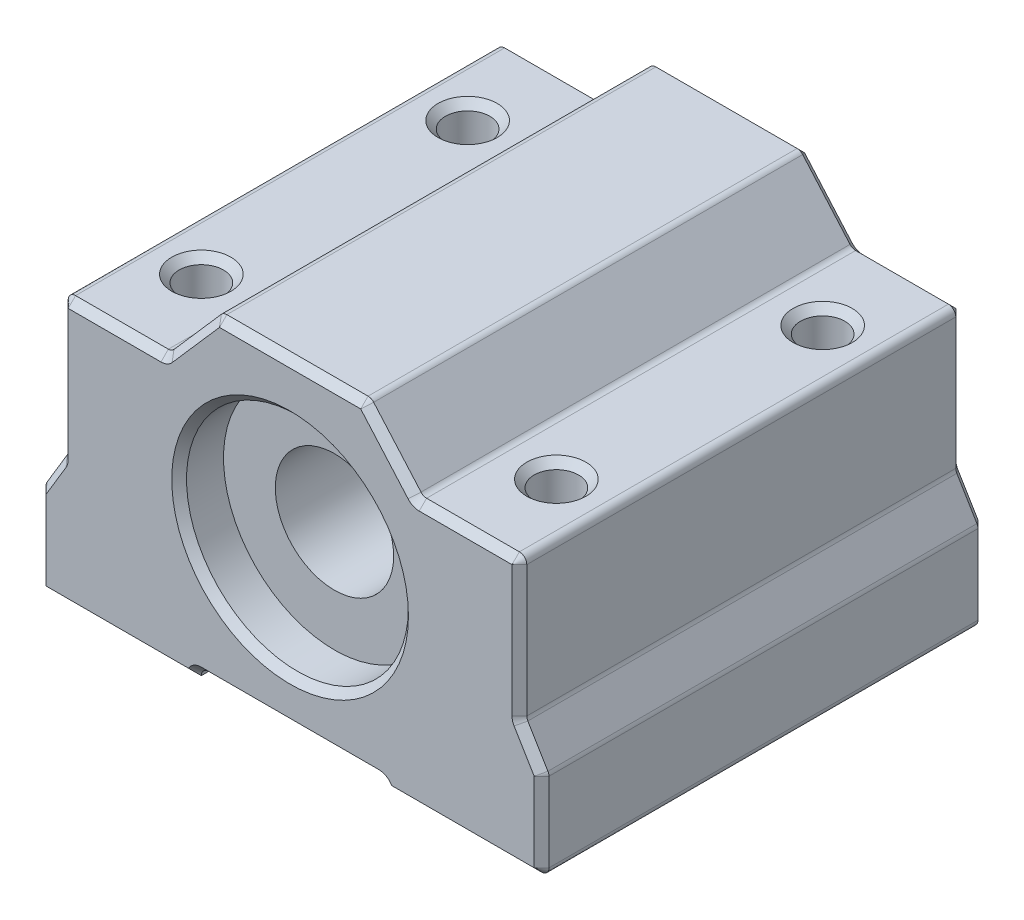
SolidWorks part; units mm, degrees
ref_plane "Front Plane" through (0, 0, 0) normal (0, 0, 1) x (1, 0, 0)
ref_plane "Top Plane" through (0, 0, 0) normal (0, 1, 0) x (1, 0, 0)
ref_plane "Right Plane" through (0, 0, 0) normal (1, 0, 0) x (0, 0, -1)
sketch "Sketch2" plane through (0, 0, 0) normal (0, 0, 1) x (1, 0, 0)
  line L17 (5, 11) -> (-5, 11)
  line L18 (-5, 11) -> (-8.5, 7)
  line L19 (-8.5, 7) -> (-15.5, 7)
  line L20 (-15.5, 7) -> (-15.5, -2.5)
  line L21 (-15.5, -2.5) -> (-17, -5)
  line L22 (-17, -5) -> (-17, -11)
  line L23 (-17, -11) -> (-6.5, -11)
  line L24 (-6.5, -11) -> (-6.5, -10.5)
  line L25 (-6.5, -10.5) -> (6.5, -10.5)
  line L26 (0, -55) -> (0, 55) construction
  line L27 (6.5, -11) -> (6.5, -10.5)
  line L28 (17, -11) -> (6.5, -11)
  line L29 (17, -5) -> (17, -11)
  line L30 (15.5, -2.5) -> (17, -5)
  line L31 (15.5, 7) -> (15.5, -2.5)
  line L32 (8.5, 7) -> (15.5, 7)
  line L33 (5, 11) -> (8.5, 7)
  circle A0 centre (0, 0) radius 7.5
  point P13 (0, -10.5)
  point P20 (0, 11)
  dimension "D12" = 15
  dimension "D1" = 31
  dimension "D2" = 0.5
  dimension "D3" = 4
  dimension "D4" = 22
  dimension "D5" = 34
  dimension "D6" = 11
  dimension "D7" = 6
  dimension "D8" = 9.5
  dimension "D9" = 13
  dimension "D10" = 10
  dimension "D11" = 7
extrude "Boss-Extrude1" add sketch "Sketch2" along normal mid plane 30
sketch "Sketch3" plane through (0, 0, 0) normal (0, 0, 1) x (1, 0, 0)
  circle A1 centre (0, 0) radius 4
  circle A2 centre (0, 0) radius 7.5
  circle A3 centre (0, 0) radius 7.5
  dimension "D2" = 8
  dimension "D1" = 0
extrude "Boss-Extrude2" add sketch "Sketch3" along normal mid plane 24 separate body
sketch "Sketch4" plane through (0, 7, 0) normal (0, 1, 0) x (1, 0, 0)
  line L0 (0, 15) -> (0, -15) construction
  line L1 (5, 15) -> (-5, 15) construction
  line L2 (5, -15) -> (-5, -15) construction
  line L3 (-15.5, 0) -> (15.5, 0) construction
  line L4 (-15.5, -15) -> (-15.5, 15) construction
  line L5 (15.5, -15) -> (15.5, 15) construction
  circle A0 centre (-12, 9) radius 1.5
  circle A1 centre (12, 9) radius 1.5
  circle A2 centre (-12, -9) radius 1.5
  circle A3 centre (12, -9) radius 1.5
  dimension "D3" = 3
  dimension "D1" = 24
  dimension "D2" = 18
extrude "Cut-Extrude1" cut sketch "Sketch4" against normal up to surface (18 mm away) up to face at (-11.75, -11, 0)
fillet "Fillet1" radius 0.5 14 edges at (6.5, -10.5, 0) (-6.5, -10.5, 0) (-17, -11, 0) (-17, -5, 0) (-15.5, -2.5, 0) (-15.5, 7, 0) (-8.5, 7, 0) (-5, 11, 0) (5, 11, 0) (8.5, 7, 0) (17, -11, 0) (17, -5, 0) (15.5, -2.5, 0) (15.5, 7, 0)
chamfer "Chamfer1" distance 0.5 angle 45 66 edges at (-12, 7, 7.5) (-12, -11, 10.5) (12, 7, 10.5) (12, -11, 10.5) (12, 7, -10.5) (12, -11, -7.5) (7.5, 0, -15) (-6.3536, -10.6464, -15) (0, -10.5, -15) (6.3536, -10.6464, -15) (11.5, -11, -15) (16.8536, -10.8536, -15) (17, -7.8192, -15) (16.9819, -5.005, -15) (16.25, -3.75, -15) (15.5181, -2.495, -15) (15.5, 2.0692, -15) (15.3536, 6.8536, -15) (11.8634, 7, -15) (8.5203, 7.0447, -15) (6.75, 9, -15) (4.9797, 10.9553, -15) (0, 11, -15) (-4.9797, 10.9553, -15) (-6.75, 9, -15) (-8.5203, 7.0447, -15) (-11.8634, 7, -15) (-15.3536, 6.8536, -15) (-15.5, 2.0692, -15) (-15.5181, -2.495, -15) (-16.25, -3.75, -15) (-16.9819, -5.005, -15) (-17, -7.8192, -15) (-16.8536, -10.8536, -15) (-11.5, -11, -15) (7.5, 0, 15) (-16.9819, -5.005, 15) (-16.25, -3.75, 15) (-15.5181, -2.495, 15) (-15.5, 2.0692, 15) (-15.3536, 6.8536, 15) (-11.8634, 7, 15) (-8.5203, 7.0447, 15) (-6.75, 9, 15) (-4.9797, 10.9553, 15) (0, 11, 15) (4.9797, 10.9553, 15) (6.75, 9, 15) (8.5203, 7.0447, 15) (11.8634, 7, 15) (15.3536, 6.8536, 15) (15.5, 2.0692, 15) (15.5181, -2.495, 15) (16.25, -3.75, 15) (16.9819, -5.005, 15) (17, -7.8192, 15) (16.8536, -10.8536, 15) (11.5, -11, 15) (6.3536, -10.6464, 15) (0, -10.5, 15) (-6.3536, -10.6464, 15) (-11.5, -11, 15) (-16.8536, -10.8536, 15) (-17, -7.8192, 15) (-12, -11, -7.5) (-12, 7, -7.5)
